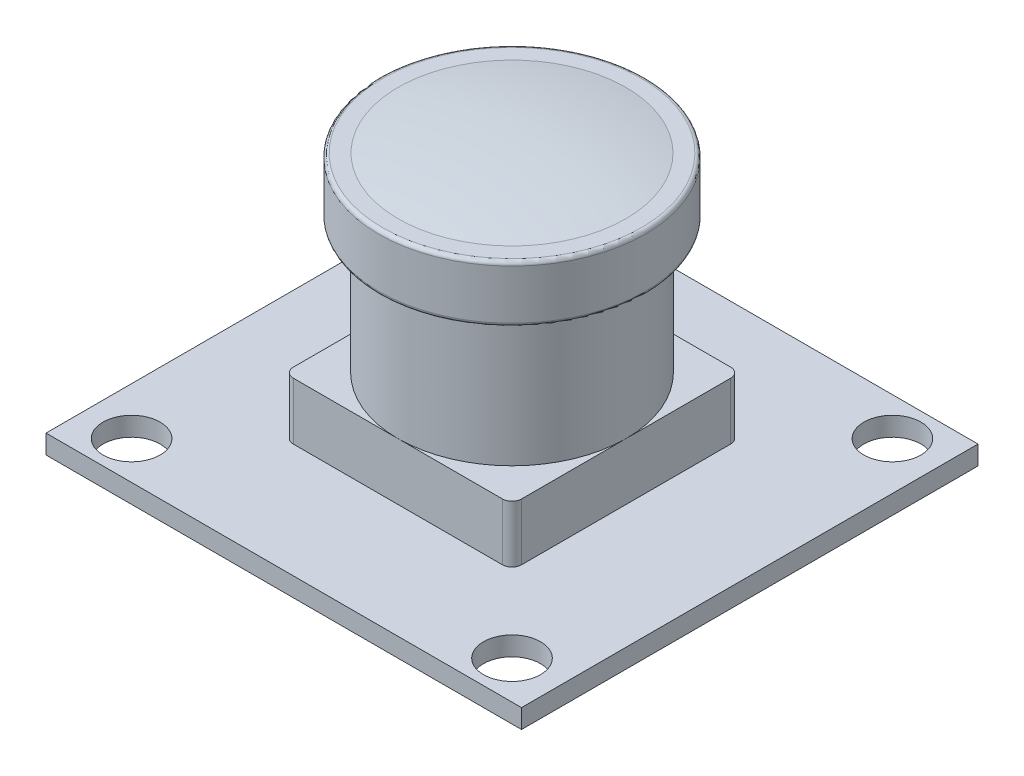
SolidWorks part; units mm, degrees
material "ABS"
ref_plane "前视基准面" through (0, 0, 0) normal (0, 0, 1) x (1, 0, 0)
ref_plane "上视基准面" through (0, 0, 0) normal (0, 1, 0) x (1, 0, 0)
ref_plane "右视基准面" through (0, 0, 0) normal (1, 0, 0) x (0, 0, -1)
sketch "草图1" plane through (0, 0, 0) normal (0, 1, 0) x (1, 0, 0)
  line L1 (-12.5, -12) -> (12.5, -12)
  line L2 (-12.5, -12) -> (-12.5, 12)
  line L3 (-12.5, 12) -> (12.5, 12)
  line L4 (12.5, -12) -> (12.5, 12)
  line L5 (-12.5, -12) -> (12.5, 12) construction
  line L6 (-12.5, 12) -> (12.5, -12) construction
  point P0 (0, 0)
  dimension "D1" = 25
  dimension "D2" = 24
extrude "凸台-拉伸1" add sketch "草图1" along normal blind 1
sketch "草图2" plane through (0, 1, 0) normal (0, 1, 0) x (1, 0, 0)
  line L1 (-6, -6) -> (6, -6)
  line L2 (-6, -6) -> (-6, 6)
  line L3 (-6, 6) -> (6, 6)
  line L4 (6, -6) -> (6, 6)
  line L5 (-6, -6) -> (6, 6) construction
  line L6 (-6, 6) -> (6, -6) construction
  point P0 (0, 0)
  dimension "D1" = 12
  dimension "D2" = 12
extrude "凸台-拉伸2" add sketch "草图2" along normal blind 3
sketch "草图3" plane through (0, 4, 0) normal (0, 1, 0) x (1, 0, 0)
  line L0 (6, 6) -> (-6, 6) construction
  circle A0 centre (0, 0) radius 6
extrude "凸台-拉伸3" add sketch "草图3" along normal blind 7
sketch "草图4" plane through (0, 11, 0) normal (0, 1, 0) x (1, 0, 0)
  circle A0 centre (0, 0) radius 7
  dimension "D1" = 14
extrude "凸台-拉伸4" add sketch "草图4" along normal blind 3
sketch "草图5" plane through (0, 0, 0) normal (0, 0, 1) x (1, 0, 0)
  line L0 (0, 0) -> (0, -2.0154) construction
  line L2 (-5.9867, 14) -> (5.9867, 14) construction
  line L3 (7, 14) -> (-7, 14) construction
  line L4 (-5.9867, 14) -> (0, 14)
  line L5 (0, 14.5476) -> (0, 14) construction
  line L6 (0, 14) -> (0, 14.5476)
  circle A0 centre (0, -18.4524) radius 33 construction
  arc A2 (0, 14.5476) -> (-5.9867, 14) centre (0, -18.4524) ccw
  dimension "D2" = 66
  dimension "D1" = 18.4524
revolve "旋转1" add sketch "草图5" angle 360 about L6
fillet "圆角1" radius 0.2 2 edges at (0, 11, 7) (0, 14, 7)
fillet "圆角2" radius 0.5 4 edges at (6, 2.5, 6) (6, 2.5, -6) (-6, 2.5, -6) (-6, 2.5, 6)
sketch "草图6" plane through (0, 0, 0) normal (0, -1, 0) x (1, 0, 0)
  line L0 (0, 12) -> (0, -12) construction
  line L1 (-12.5, 12) -> (12.5, 12) construction
  line L2 (12.5, -12) -> (-12.5, -12) construction
  line L3 (-12.5, 0) -> (12.5, 0) construction
  line L4 (-12.5, -12) -> (-12.5, 12) construction
  line L5 (12.5, 12) -> (12.5, -12) construction
  circle A0 centre (-10, 10) radius 1.5
  circle A1 centre (10, 10) radius 1.5
  circle A2 centre (-10, -10) radius 1.5
  circle A3 centre (10, -10) radius 1.5
  dimension "D1" = 3
  dimension "D2" = 10
  dimension "D3" = 10
extrude "切除-拉伸1" cut sketch "草图6" against normal up to next
